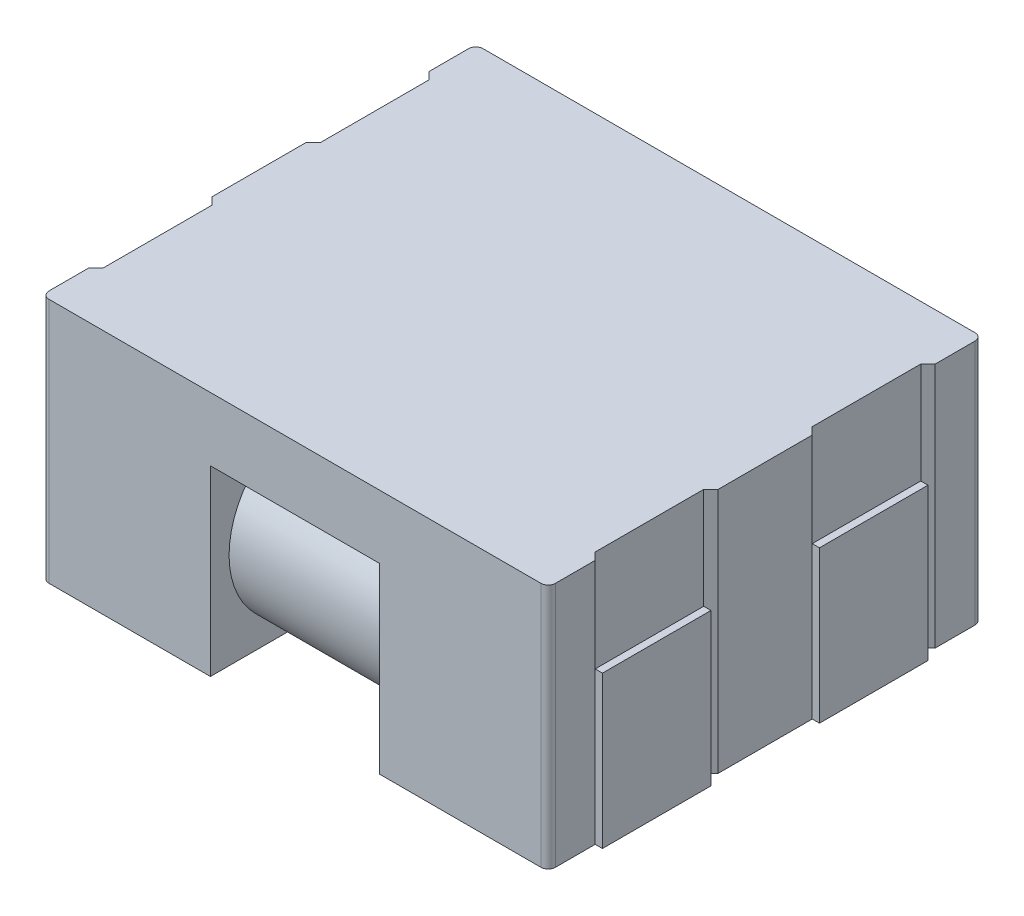
SolidWorks part; units mm, degrees
ref_plane "Front Plane" through (0, 0, 0) normal (0, 0, 1) x (1, 0, 0)
ref_plane "Top Plane" through (0, 0, 0) normal (0, 1, 0) x (1, 0, 0)
ref_plane "Right Plane" through (0, 0, 0) normal (1, 0, 0) x (0, 0, -1)
sketch "Sketch2" plane through (0, 0, 0) normal (0, 1, 0) x (1, 0, 0)
  line L0 (0, 3) -> (7, 3) construction
  line L1 (0, 0) -> (7, 0) construction
  line L2 (0, 0) -> (0, 6) construction
  line L3 (0, 6) -> (7, 6) construction
  line L4 (7, 0) -> (7, 6) construction
  line L5 (3.5, 6) -> (3.5, 0) construction
  line L6 (7, 3.75) -> (5.5, 3.75)
  line L7 (0, 5.25) -> (1.5, 5.25)
  line L8 (0, 5.25) -> (0, 3.75)
  line L9 (0, 3.75) -> (1.5, 3.75)
  line L10 (1.5, 5.25) -> (1.5, 3.75)
  line L11 (5.5, 5.25) -> (5.5, 3.75)
  line L12 (7, 5.25) -> (5.5, 5.25)
  line L13 (7, 5.25) -> (7, 3.75)
  line L14 (7, 0.75) -> (7, 2.25)
  line L15 (7, 0.75) -> (5.5, 0.75)
  line L16 (5.5, 0.75) -> (5.5, 2.25)
  line L17 (1.5, 0.75) -> (1.5, 2.25)
  line L18 (0, 2.25) -> (1.5, 2.25)
  line L19 (0, 0.75) -> (0, 2.25)
  line L20 (0, 0.75) -> (1.5, 0.75)
  line L21 (7, 2.25) -> (5.5, 2.25)
  dimension "D1" = 6
  dimension "D2" = 7
  dimension "D3" = 2
  dimension "D4" = 0.75
  dimension "D5" = 1.5
extrude "Boss-Extrude1" add sketch "Sketch2" along normal blind 0.1
sketch "Sketch5" plane through (0, 0, 0) normal (0, 1, 0) x (1, 0, 0)
  line L1 (0, 0) -> (7, 0)
  line L2 (0, 0) -> (0, 6)
  line L3 (0, 6) -> (7, 6)
  line L4 (7, 0) -> (7, 6)
extrude "Boss-Extrude2" add sketch "Sketch5" along normal offset from surface (3.4 mm away) 3.5 from vertex separate body up to face at (0.75, 0, -4.5) starting at point (0, 0.1, -0.75)
sketch "Sketch6" plane through (0, 3.5, 0) normal (0, 1, 0) x (1, 0, 0)
  line L0 (7, 0) -> (7, 6) construction
  line L1 (7, 0.75) -> (6.9, 0.75)
  line L2 (7, 0.75) -> (7, 2.25)
  line L3 (7, 2.25) -> (6.9, 2.25)
  line L4 (6.9, 0.75) -> (6.9, 2.25)
  line L5 (7, 3) -> (0, 3) construction
  line L6 (0, 6) -> (0, 0) construction
  line L7 (6.9, 5.25) -> (6.9, 3.75)
  line L8 (7, 3.75) -> (6.9, 3.75)
  line L9 (7, 5.25) -> (7, 3.75)
  line L10 (7, 5.25) -> (6.9, 5.25)
  line L11 (3.5, 6) -> (3.5, 0) construction
  line L12 (7, 6) -> (0, 6) construction
  line L13 (0, 0) -> (7, 0) construction
  line L14 (0, 5.25) -> (0.1, 5.25)
  line L15 (0, 5.25) -> (0, 3.75)
  line L16 (0, 3.75) -> (0.1, 3.75)
  line L17 (0.1, 5.25) -> (0.1, 3.75)
  line L18 (0.1, 0.75) -> (0.1, 2.25)
  line L19 (0, 2.25) -> (0.1, 2.25)
  line L20 (0, 0.75) -> (0, 2.25)
  line L21 (0, 0.75) -> (0.1, 0.75)
  dimension "D1" = 0.1
extrude "Cut-Extrude1" cut sketch "Sketch6" against normal up to vertex (3.4 mm away) up to point (7, 0.1, -0.75)
sketch "Sketch7" plane through (0, 0.1, 0) normal (0, 1, 0) x (1, 0, 0)
  line L1 (7, 0.75) -> (6.9, 0.75)
  line L2 (7, 0.75) -> (7, 2.25)
  line L3 (7, 2.25) -> (6.9, 2.25)
  line L4 (6.9, 0.75) -> (6.9, 2.25)
  line L5 (7, 3.75) -> (6.9, 3.75)
  line L6 (7, 3.75) -> (7, 5.25)
  line L7 (7, 5.25) -> (6.9, 5.25)
  line L8 (6.9, 3.75) -> (6.9, 5.25)
  line L9 (0, 0.75) -> (0.1, 0.75)
  line L10 (0, 0.75) -> (0, 2.25)
  line L11 (0, 2.25) -> (0.1, 2.25)
  line L12 (0.1, 0.75) -> (0.1, 2.25)
  line L13 (0, 3.75) -> (0.1, 3.75)
  line L14 (0, 3.75) -> (0, 5.25)
  line L15 (0, 5.25) -> (0.1, 5.25)
  line L16 (0.1, 3.75) -> (0.1, 5.25)
extrude "Boss-Extrude4" add sketch "Sketch7" along normal blind 2 separate body
combine bodies "Combine1" operation type add bodies to combine 112 104
combine bodies "Combine2" operation type add bodies to combine 101 113
combine bodies "Combine3" operation type add bodies to combine 102 111
combine bodies "Combine4" operation type add bodies to combine 103 110
chamfer "Chamfer1" distance 0.1 angle 45 8 edges at (0, 1.8, -0.75) (0, 1.8, -2.25) (0, 1.8, -3.75) (0, 1.8, -5.25) (7, 1.8, -5.25) (7, 1.8, -0.75) (7, 1.8, -3.75) (7, 1.8, -2.25)
fillet "Fillet1" radius 0.1 4 edges at (0, 1.8, -6) (0, 1.8, 0) (7, 1.8, -6) (7, 1.8, 0)
sketch "Sketch8" plane through (0, 0, 0) normal (0, 0, 1) x (1, 0, 0)
  line L0 (0.1, 0.1) -> (6.9, 0.1) construction
  line L1 (2.3316, 0.1) -> (4.6684, 0.1)
  line L2 (2.3316, 0.1) -> (2.3316, 2.6229)
  line L3 (2.3316, 2.6229) -> (4.6684, 2.6229)
  line L4 (3.5, 0.1) -> (3.5, 2.6229) construction
  line L6 (4.6684, 0.1) -> (4.6684, 2.6229)
  dimension "D1" = 1.1684
  dimension "D2" = 2.5229
extrude "Cut-Extrude2" cut sketch "Sketch8" against normal through all
sketch "Sketch9" plane through (4.6684, 0, 0) normal (-1, 0, 0) x (0, 0, 1)
  line L0 (-3, 2.6229) -> (-3, 0.1) construction
  line L1 (-6, 2.6229) -> (0, 2.6229) construction
  line L2 (-6, 0.1) -> (0, 0.1) construction
  circle A0 centre (-1.5, 1.4229) radius 1.2423
  circle A1 centre (-4.5, 1.4229) radius 1.2423
  dimension "D1" = 2.4846
  dimension "D2" = 1.5
  dimension "D3" = 1.2
extrude "Boss-Extrude5" add sketch "Sketch9" along normal up to vertex (2.3368 mm away) separate body up to point (2.3316, 0.1, 0)
combine bodies "Combine6" operation type subtract main body 118 bodies to subtract 119 121
sketch "Sketch10" plane through (2.3316, 0, 0) normal (1, 0, 0) x (0, 0, -1)
  circle A0 centre (1.5, 1.4229) radius 1.2423
  arc A1 (1.8214, 2.6229) -> (1.1786, 2.6229) centre (1.5, 1.4229) ccw construction
  circle A2 centre (4.5, 1.4229) radius 1.2423
  arc A3 (4.8214, 2.6229) -> (4.1786, 2.6229) centre (4.5, 1.4229) ccw construction
extrude "Boss-Extrude6" add sketch "Sketch10" along normal up to vertex (2.3368 mm away) separate body up to point (4.6684, 0.1, 0)
